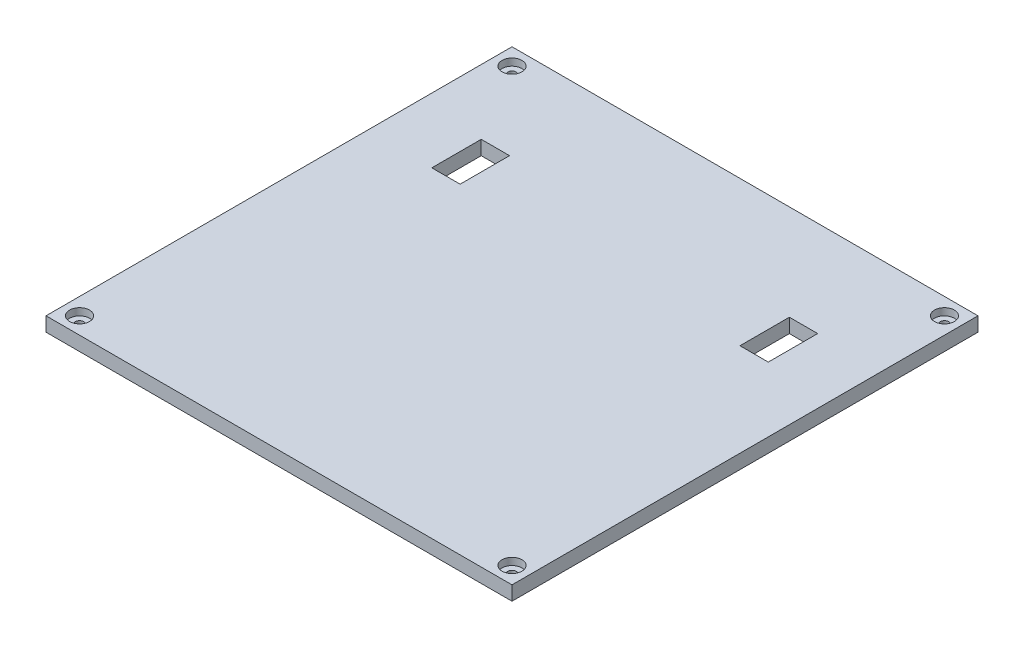
SolidWorks part; units mm, degrees
material "Custom Plastic"
ref_plane "Front Plane" through (0, 0, 0) normal (0, 0, 1) x (1, 0, 0)
ref_plane "Top Plane" through (0, 0, 0) normal (0, 1, 0) x (1, 0, 0)
ref_plane "Right Plane" through (0, 0, 0) normal (1, 0, 0) x (0, 0, -1)
sketch "Sketch1" plane through (0, 0, 0) normal (0, 1, 0) x (1, 0, 0)
  line L1 (0, 0) -> (416.08, 0)
  line L2 (0, 0) -> (0, 416.08)
  line L3 (0, 416.08) -> (416.08, 416.08)
  line L4 (416.08, 0) -> (416.08, 416.08)
extrude "Boss-Extrude1" add sketch "Sketch1" along normal blind 12.7 contours L2 L1 L4 L3
sketch "Sketch2" plane through (0, 12.7, 0) normal (0, 1, 0) x (1, 0, 0)
  line L8 (0, 0) -> (416.08, 0) construction
  line L9 (0, 0) -> (0, 416.08) construction
  circle A0 centre (14.986, 14.986) radius 3.683
  dimension "D5" = 7.366
  dimension "D1" = 14.986
  dimension "D2" = 14.986
extrude "Cut-Extrude1" cut sketch "Sketch2" against normal through all
sketch "Sketch3" plane through (0, 12.7, 0) normal (0, 1, 0) x (1, 0, 0)
  circle A0 centre (14.986, 14.986) radius 8.89
  dimension "D1" = 17.78
extrude "Cut-Extrude2" cut sketch "Sketch3" against normal mid plane 12.7
ref_plane "Plane1" through (208.04, 0, 0) normal (-1, 0, 0) x (0, 0, 1)
ref_plane "Plane2" through (0, 0, -208.04) normal (0, 0, -1) x (-1, 0, 0)
mirror "Mirror1" about plane through (0, 0, -208.04) normal (0, 0, -1) of "Cut-Extrude2", "Cut-Extrude1" second plane through (208.04, 0, 0) second plane normal (-1, 0, 0)
sketch "Sketch4" plane through (0, 0, 0) normal (0, -1, 0) x (1, 0, 0)
  line L0 (208.04, -416.08) -> (208.04, -105.878) construction
  line L1 (57.8338, -286.6447) -> (83.1069, -286.6447)
  line L2 (57.8338, -286.6447) -> (57.8338, -330.7655)
  line L3 (57.8338, -330.7655) -> (83.1069, -330.7655)
  line L4 (83.1069, -286.6447) -> (83.1069, -330.7655)
  line L5 (57.8338, -286.6447) -> (83.1069, -330.7655) construction
  line L6 (57.8338, -330.7655) -> (83.1069, -286.6447) construction
  line L7 (0, -416.08) -> (416.08, -416.08) construction
  line L8 (358.2462, -330.7655) -> (332.9731, -330.7655)
  line L9 (332.9731, -286.6447) -> (332.9731, -330.7655)
  line L10 (358.2462, -286.6447) -> (332.9731, -286.6447)
  line L11 (358.2462, -286.6447) -> (358.2462, -330.7655)
  point P0 (70.4703, -308.7051)
extrude "Cut-Extrude3" cut sketch "Sketch4" against normal through all
